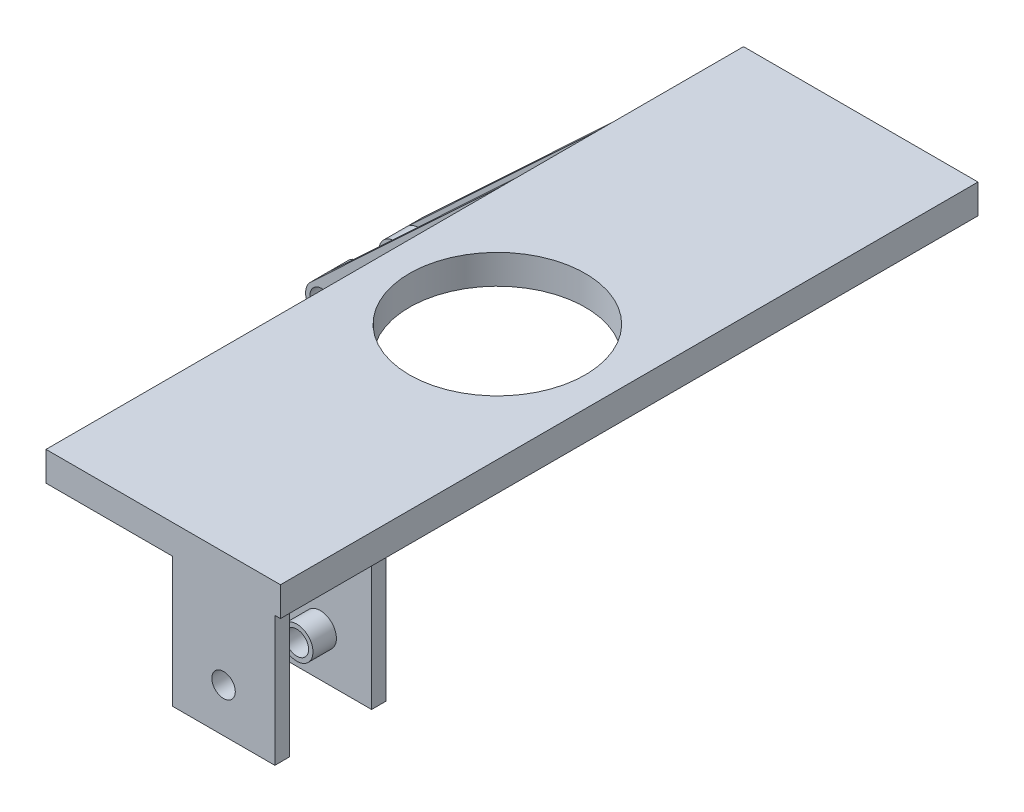
SolidWorks part; units mm, degrees
ref_plane "Front Plane" through (0, 0, 0) normal (0, 0, 1) x (1, 0, 0)
ref_plane "Top Plane" through (0, 0, 0) normal (0, 1, 0) x (1, 0, 0)
ref_plane "Right Plane" through (0, 0, 0) normal (1, 0, 0) x (0, 0, -1)
sketch3d "3DSketch1"
  line L0 (717.75, 650, 110) -> (717.75, 574.8784, 110) construction
  line L1 (738.34, 550.67, 205) -> (709.53, 565, 5)
  line L2 (616.52, 525.27, 49.7) -> (714.325, 562.615, 38.287)
  circle A0 centre (717.75, 650, 110) radius 260
  point P0 (717.75, 650, 110)
  point P2 (616.52, 525.27, 49.7)
  point P4 (709.53, 565, 5)
  point P6 (738.34, 550.67, 205)
  point P9 (717.75, 910, 110)
  dimension "D1" = 520
ref_plane "UB" through (0, 0, 205) normal (0, 0, 1) x (1, 0, 0)
ref_plane "LB" through (0, 0, 5) normal (0, 0, 1) x (1, 0, 0)
ref_plane "TRB" through (0, 0, 49.7) normal (0, 0, 1) x (1, 0, 0)
ref_plane "Plane4" through (0, 565, 0) normal (0, 1, 0) x (1, 0, 0)
ref_plane "HubPlane" through (0, 580, 0) normal (0, 1, 0) x (1, 0, 0)
sketch "Sketch1" plane through (0, 580, 0) normal (0, 1, 0) x (1, 0, 0)
  line L0 (738.34, -199) -> (738.34, -211) construction
  line L1 (743.4791, -211) -> (733.2009, -211) construction
  line L2 (743.4791, -199) -> (733.2009, -199) construction
  line L3 (738.34, -191) -> (738.34, -219) construction
  line L8 (755.84, -219) -> (720.84, -219)
  line L9 (709.53, 9) -> (709.53, -19) construction
  line L10 (727.03, -19) -> (692.03, -19)
  line L11 (727.03, 9) -> (692.03, 9)
  line L12 (755.84, -191) -> (720.84, -191)
  line L13 (738.34, -219) -> (738.34, -224) construction
  line L14 (755.84, -224) -> (720.84, -224)
  line L15 (720.84, -224) -> (720.84, -219)
  line L16 (755.84, -224) -> (755.84, -219)
  line L17 (738.34, -191) -> (738.34, -186) construction
  line L18 (755.84, -186) -> (720.84, -186)
  line L19 (755.84, -191) -> (755.84, -186)
  line L20 (720.84, -191) -> (720.84, -186)
  line L21 (709.53, -19) -> (709.53, -24) construction
  line L22 (727.03, -24) -> (692.03, -24)
  line L23 (692.03, -24) -> (692.03, -19)
  line L24 (727.03, -24) -> (727.03, -19)
  line L25 (709.53, 9) -> (709.53, 14) construction
  line L26 (727.03, 14) -> (692.03, 14)
  line L27 (692.03, 9) -> (692.03, 14)
  line L28 (727.03, 9) -> (727.03, 14)
  line L29 (720.84, -219) -> (720.84, -191)
  line L30 (755.84, -219) -> (755.84, -191)
  line L31 (692.03, -19) -> (692.03, 9)
  line L32 (727.03, -19) -> (727.03, 9)
  line L33 (757.75, 14) -> (757.75, -224)
  line L34 (677.75, -224) -> (720.84, -224)
  line L35 (757.75, -224) -> (755.84, -224)
  line L36 (757.75, 14) -> (727.03, 14)
  line L37 (616.52, -49.7) -> (616.52, -30.7) construction
  line L38 (677.75, -224) -> (677.75, 14)
  line L39 (599.02, -68.7) -> (634.02, -68.7)
  line L40 (599.02, -68.7) -> (599.02, -30.7)
  line L41 (599.02, -30.7) -> (634.02, -30.7)
  line L42 (634.02, -68.7) -> (634.02, -30.7)
  line L43 (599.02, -68.7) -> (634.02, -30.7) construction
  line L44 (599.02, -30.7) -> (634.02, -68.7) construction
  line L46 (677.75, 14) -> (692.03, 14)
  circle A0 centre (738.34, -205) radius 7.9 construction
  circle A1 centre (709.53, -5) radius 7.9 construction
  circle A2 centre (616.52, -49.7) radius 7.9
  circle A3 centre (717.75, -110) radius 30
  point P0 (616.52, -49.7)
  point P2 (709.53, -5)
  point P4 (717.75, -110)
  point P6 (738.34, -205)
  point P19 (738.34, -211)
  point P20 (738.34, -205)
  point P23 (738.34, -199)
  point P26 (738.34, -205)
  point P28 (738.34, -219)
  point P31 (709.53, -5)
  point P35 (709.53, -19)
  point P38 (709.53, 9)
  point P41 (738.34, -199)
  point P42 (738.34, -191)
  point P46 (738.34, -224)
  point P50 (738.34, -186)
  point P54 (709.53, -24)
  point P58 (709.53, 14)
  point P68 (616.52, -30.7)
  dimension "D1" = 15.8
  dimension "D13" = 60
  dimension "D2" = 12
  dimension "D3" = 28
  dimension "D4" = 35
  dimension "D5" = 28
  dimension "D6" = 35
  dimension "D7" = 35
  dimension "D8" = 35
  dimension "D9" = 5
  dimension "D10" = 5
  dimension "D11" = 5
  dimension "D12" = 5
  dimension "D14" = 19
  dimension "D15" = 35
  dimension "D16" = 40
  dimension "D17" = 40
sketch "Sketch2" plane through (0, 0, 205) normal (0, 0, 1) x (1, 0, 0)
  line L0 (755.84, 580) -> (720.84, 580) construction
  line L5 (755.84, 580) -> (720.84, 580)
  line L6 (738.34, 550.67) -> (738.34, 535.67) construction
  line L7 (720.84, 535.67) -> (755.84, 535.67)
  line L8 (755.84, 535.67) -> (755.84, 580)
  line L9 (720.84, 535.67) -> (720.84, 580)
  circle A0 centre (738.34, 550.67) radius 4
  circle A1 centre (738.34, 550.67) radius 5.5
  point P0 (738.34, 550.67)
  point P2 (738.34, 550.67)
  point P9 (738.34, 535.67)
  dimension "D3" = 8
  dimension "D4" = 11
  dimension "D1" = 15
  dimension "D2" = 35
sketch "Sketch3" plane through (0, 0, 5) normal (0, 0, 1) x (1, 0, 0)
  line L0 (727.03, 580) -> (692.03, 580) construction
  line L1 (727.03, 580) -> (692.03, 580)
  line L2 (709.53, 565) -> (709.53, 550) construction
  line L4 (692.03, 550) -> (727.03, 550)
  line L5 (727.03, 550) -> (727.03, 580)
  line L6 (692.03, 550) -> (692.03, 580)
  circle A0 centre (709.53, 565) radius 5.5
  circle A1 centre (709.53, 565) radius 4
  point P0 (709.53, 565)
  point P8 (709.53, 550)
  dimension "D2" = 11
  dimension "D3" = 8
  dimension "D1" = 15
extrude "Boss-Extrude1" add sketch "Sketch1" along normal blind 10 contours L46 L38 L34 L15 L29 L20 L18 L19 L30 L16 L35 L33 L36 L28 L32 L24 L22 L23 L31 L27 A3 | L11 L28 L26 L27 | L10 L32 L11 L31 | L22 L24 L10 L23 | L20 L12 L19 L18 | L8 L30 L12 L29 | L14 L16 L8 L15 region at (738.34, 580, 221.5) region at (756.0911, 580, 205) region at (738.34, 580, 205) region at (738.34, 580, 188.5) region at (709.53, 580, -11.5) region at (709.53, 580, 5) region at (709.53, 580, 21.5)
extrude "Boss-Extrude2" add sketch "Sketch2" along normal up to surface (19 mm away) and the other way up to vertex (19 mm away) contours A1 L7 L8 L5 L9 region at (738.34, 558.3025, 205) up to face at (717.75, 585, 224) other way up to point (720.84, 580, 186)
extrude "Cut-Extrude1" cut sketch "Sketch2<4>" against normal mid plane 28 contours A1 L7 L8 L5 L9 region at (738.34, 558.3025, 205)
sketch "Sketch2<4>" plane through (0, 0, 205) normal (0, 0, 1) x (1, 0, 0) same geometry as "Sketch2"
extrude "Boss-Extrude3" add sketch "Sketch3" along normal mid plane 38 contours A0 L4 L5 L1 L6 region at (726.569, 565, 5)
extrude "Cut-Extrude2" cut sketch "Sketch3<3>" against normal mid plane 28 contours A0 L4 L5 L1 L6 region at (726.569, 565, 5)
sketch "Sketch3<3>" plane through (0, 0, 5) normal (0, 0, 1) x (1, 0, 0) same geometry as "Sketch3"
extrude "Boss-Extrude4" add sketch "Sketch2<5>" along normal mid plane 38 contours A0 A1 region at (732.9956, 550.67, 205)
sketch "Sketch2<5>" plane through (0, 0, 205) normal (0, 0, 1) x (1, 0, 0) same geometry as "Sketch2"
extrude "Cut-Extrude3" cut sketch "Sketch2<6>" against normal mid plane 12 contours A0 A1 region at (732.9956, 550.67, 205)
sketch "Sketch2<6>" plane through (0, 0, 205) normal (0, 0, 1) x (1, 0, 0) same geometry as "Sketch2"
extrude "Boss-Extrude5" add sketch "Sketch3<4>" along normal mid plane 38 contours A1 A0 region at (704.1856, 565, 5)
sketch "Sketch3<4>" plane through (0, 0, 5) normal (0, 0, 1) x (1, 0, 0) same geometry as "Sketch3"
extrude "Cut-Extrude4" cut sketch "Sketch3<5>" against normal mid plane 12 contours A1 A0 region at (704.1856, 565, 5)
sketch "Sketch3<5>" plane through (0, 0, 5) normal (0, 0, 1) x (1, 0, 0) same geometry as "Sketch3"
sketch "Sketch5" plane through (0, 0, 49.7) normal (0, 0, 1) x (1, 0, 0)
  line L0 (677.75, 590) -> (677.75, 580) construction
  line L1 (677.75, 590) -> (677.75, 580)
  line L2 (677.75, 580) -> (620.4517, 521.424)
  line L3 (677.75, 590) -> (612.7653, 529.289)
  circle A0 centre (616.52, 525.27) radius 4
  circle A1 centre (616.52, 525.27) radius 5.5
  point P2 (616.52, 525.27)
  dimension "D1" = 8
  dimension "D2" = 11
extrude "Boss-Extrude6" add sketch "Sketch5" along normal mid plane 38 contours A1 L2 L1 L3 | A1 A0 region at (646.6862, 554.8085, 49.7) region at (618.6488, 530.1721, 49.7)
extrude "Cut-Extrude5" cut sketch "Sketch5<5>" against normal mid plane 28 contours A1 L2 L1 L3 region at (646.6862, 554.8085, 49.7)
sketch "Sketch5<5>" plane through (0, 0, 49.7) normal (0, 0, 1) x (1, 0, 0) same geometry as "Sketch5"
extrude "Cut-Extrude6" cut sketch "Sketch5<6>" against normal mid plane 12 contours A1 A0 region at (618.6488, 530.1721, 49.7)
sketch "Sketch5<6>" plane through (0, 0, 49.7) normal (0, 0, 1) x (1, 0, 0) same geometry as "Sketch5"
